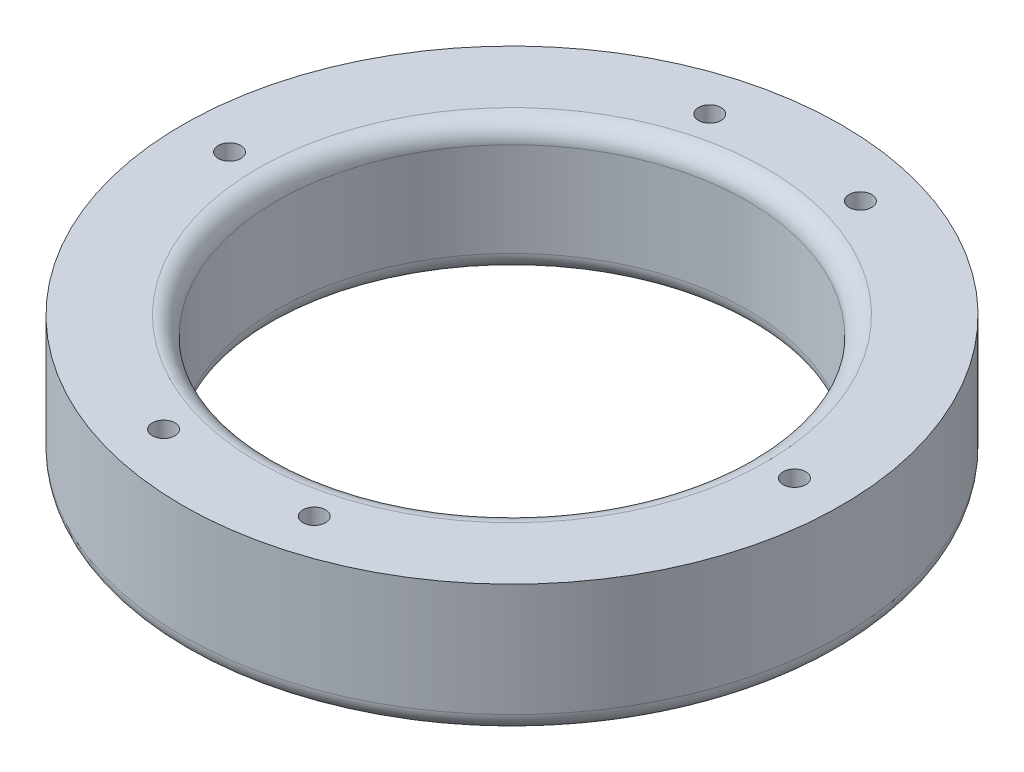
SolidWorks part; units mm, degrees
ref_plane "Спереди" through (0, 0, 0) normal (0, 0, 1) x (1, 0, 0)
ref_plane "Сверху" through (0, 0, 0) normal (0, 1, 0) x (1, 0, 0)
ref_plane "Справа" through (0, 0, 0) normal (1, 0, 0) x (0, 0, -1)
sketch "Sketch1" plane through (0, 0, 0) normal (0, 1, 0) x (1, 0, 0)
  line L0 (-11.7247, 0) -> (16.8046, 0) construction
  line L1 (0, 7.3106) -> (0, -15.7423) construction
  circle A0 centre (0, 0) radius 17.5
  circle A1 centre (-4, 14.5) radius 0.6
  circle A2 centre (-4, -14.5) radius 0.6
  circle A3 centre (15, 0) radius 0.6
  circle A4 centre (-15, 0) radius 0.6
  circle A5 centre (4, 14.5) radius 0.6
  circle A6 centre (4, -14.5) radius 0.6
  circle A8 centre (0, 0) radius 12.5
  dimension "D1" = 35
  dimension "D7" = 1.2
  dimension "D8" = 1.2
  dimension "D9" = 1.2
  dimension "D10" = 1.2
  dimension "D11" = 1.2
  dimension "D12" = 1.2
  dimension "D18" = 25
  dimension "D2" = 15
  dimension "D3" = 4
  dimension "D4" = 14.5
  dimension "D5" = 14.5
  dimension "D6" = 4
  dimension "D13" = 15
  dimension "D14" = 4
  dimension "D15" = 14.5
  dimension "D16" = 14.5
  dimension "D17" = 4
extrude "Boss-Extrude1" add sketch "Sketch1" along normal blind 7
fillet "Fillet1" radius 1 3 edges at (0, 0, 17.5) (0, 0, 12.5) (0, 7, 12.5)
